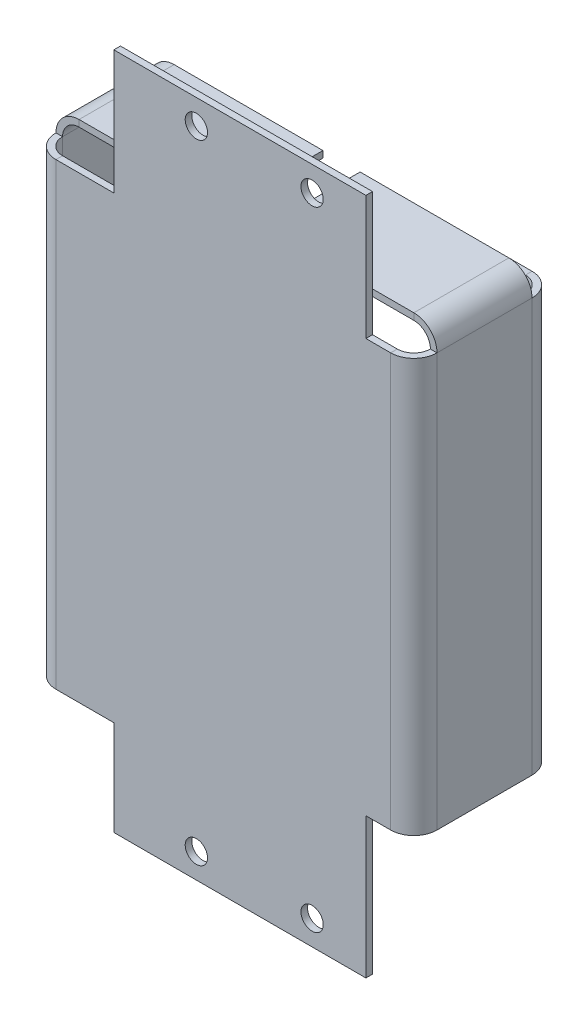
SolidWorks part; units mm, degrees
note: The reader was unsure of these and kept them because the rebuilt part matched: flange length of "Edge-Flange1", "Edge-Flange4", "Edge-Flange5".
ref_plane "Front Plane" through (0, 0, 0) normal (0, 0, 1) x (1, 0, 0)
ref_plane "Top Plane" through (0, 0, 0) normal (0, 1, 0) x (1, 0, 0)
ref_plane "Right Plane" through (0, 0, 0) normal (1, 0, 0) x (0, 0, -1)
sketch "Sketch1" plane through (0, 0, 0) normal (0, 0, 1) x (1, 0, 0)
  line L0 (16.25, 0) -> (16.25, -17)
  line L1 (21.25, 50) -> (16.25, 50)
  line L2 (21.25, 50) -> (21.25, 0)
  line L3 (21.25, 0) -> (16.25, 0)
  line L4 (-23.25, 50) -> (-23.25, -5.5)
  line L5 (16.25, -17) -> (-14.25, -17)
  line L6 (-14.25, -17) -> (-14.25, -5.5)
  line L7 (16.25, 50) -> (16.25, 65)
  line L9 (16.25, 65) -> (-14.25, 65)
  line L10 (-14.25, 65) -> (-14.25, 50)
  line L11 (-14.25, -5.5) -> (-23.25, -5.5)
  line L12 (-14.25, 50) -> (-23.25, 50)
  circle A0 centre (9.7378, -14) radius 1.35
  circle A1 centre (-4.2622, -14) radius 1.35
  circle A2 centre (9.7378, 62) radius 1.35
  circle A3 centre (-4.2622, 62) radius 1.35
  dimension "D6" = 6.5122
  dimension "D7" = 3
  dimension "D8" = 2.7
  dimension "D9" = 3
  dimension "D10" = 14
  dimension "D11" = 76
  dimension "D12" = 14
  dimension "D13" = 3
  dimension "D14" = 3
  dimension "D1" = 50
  dimension "D2" = 9
  dimension "D3" = 82
  dimension "D4" = 17
  dimension "D5" = 30.5
  dimension "D15" = 11.5
  dimension "D16" = 5
sheet metal parameters "Sheet-Metal1" thickness 0.8 parameters "D1"=2
base flange "Base-Flange1" sketch "Sketch1" thickness 0.8 reverse thickness direction yes parameters "D1"=2
edge flange "Edge-Flange1" sketch "Sketch6" flange profiles "Sketch6", "Sketch11" flange angle 90 flange length 13.5 flange position material outside bend radius 2 thickness 0.8 parameters "D6"=10, "D8"=1
sketch "Sketch6" plane through (21.25, 0, 0) normal (-1, 0, 0) x (0, 1, 0)
  line L2 (0, 0) -> (0, 13.5)
  line L3 (0, 13.5) -> (50, 13.5)
  line L4 (50, 13.5) -> (50, 0)
  line L6 (50, 0) -> (0, 0) construction
  line L7 (50, 0) -> (0, 0)
sketch "Sketch11" plane through (-23.25, 0, 0) normal (1, 0, 0) x (0, -1, 0)
  line L0 (5.5, 0) -> (-50, 0) construction
  line L1 (5.5, 0) -> (-50, 0)
  line L2 (5.5, 0) -> (5.5, 13.5)
  line L3 (5.5, 13.5) -> (-50, 13.5)
  line L4 (-50, 13.5) -> (-50, 0)
bend "EdgeBend1" bend radius 2 bend angle 90 parameters "D5"=1
bend "EdgeBend3" bend radius 2 bend angle 90 parameters "D5"=2
edge flange "Edge-Flange4" sketch "Sketch19" flange profiles "Sketch19", "Sketch20" flange angle 90 flange length 20 flange position bend outside bend radius 2 thickness 0.8 parameters "D6"=10, "D8"=1
sketch "Sketch19" plane through (21.25, 50, 0) normal (0, -1, 0) x (0, 0, 1)
  line L2 (-13.5, 0) -> (-13.5, 20)
  line L3 (-13.5, 20) -> (-2, 20)
  line L4 (-2, 20) -> (-2, 0)
  line L6 (-2, 0) -> (-13.5, 0) construction
  line L7 (-2, 0) -> (-13.5, 0)
sketch "Sketch20" plane through (-23.25, 50, 0) normal (0, -1, 0) x (0, 0, -1)
  line L0 (13.5, 0) -> (2, 0) construction
  line L1 (13.5, 0) -> (2, 0)
  line L2 (13.5, 0) -> (13.5, 20)
  line L3 (13.5, 20) -> (2, 20)
  line L4 (2, 20) -> (2, 0)
bend "EdgeBend5" bend radius 2 bend angle 90 parameters "D5"=3
bend "EdgeBend6" bend radius 2 bend angle 90 parameters "D5"=4
edge flange "Edge-Flange5" sketch "Sketch28" flange profiles "Sketch28", "Sketch29" flange angle 90 flange length 10 flange position bend outside bend radius 2 thickness 0.8 parameters "D6"=10, "D8"=1
sketch "Sketch28" plane through (21.25, 0, -13.5) normal (0, 0, 1) x (0, 1, 0)
  line L1 (50, 0) -> (0, 0) construction
  line L2 (0, 0) -> (0, 10)
  line L3 (0, 10) -> (50, 10)
  line L4 (50, 10) -> (50, 0)
  line L5 (50, 0) -> (0, 0)
sketch "Sketch29" plane through (-23.25, 0, -13.5) normal (0, 0, 1) x (0, -1, 0)
  line L0 (5.5, 0) -> (-50, 0) construction
  line L1 (5.5, 0) -> (-50, 0)
  line L2 (5.5, 0) -> (5.5, 10)
  line L3 (5.5, 10) -> (-50, 10)
  line L4 (-50, 10) -> (-50, 0)
bend "EdgeBend7" bend radius 2 bend angle 90 parameters "D5"=5
bend "EdgeBend8" bend radius 2 bend angle 90 parameters "D5"=6
flat pattern "Flat-Pattern1" [suppressed]
sketch "Bend-Lines1" plane through (0, 0, 0.8) normal (0, 0, 1) x (1, 0, 0)
  line L0 (-38.3766, -5.5) -> (-38.3766, 50) construction
  line L1 (36.3766, 50) -> (36.3766, 0) construction
  line L2 (-36.5011, 51.8755) -> (-25.0011, 51.8755) construction
  line L3 (23.0011, 51.8755) -> (34.5011, 51.8755) construction
  line L4 (-23.1255, -5.5) -> (-23.1255, 50) construction
  line L5 (21.1255, 50) -> (21.1255, 0) construction
  line L6 (-38.3766, -5.5) -> (-38.3766, 50) construction
  line L7 (36.3766, 50) -> (36.3766, 0) construction
  line L8 (-36.5011, 51.8755) -> (-25.0011, 51.8755) construction
  line L9 (23.0011, 51.8755) -> (34.5011, 51.8755) construction
  line L10 (-23.1255, -5.5) -> (-23.1255, 50) construction
  line L11 (21.1255, 50) -> (21.1255, 0) construction
sketch3d "Bounding-Box1" [suppressed]
  line L0 (-69.5021, -17, 0) -> (25.0021, -17, 0) construction
  line L1 (-69.5021, 71.7511, 0) -> (25.0021, 71.7511, 0) construction
  line L2 (-69.5021, -17, 0) -> (-69.5021, 71.7511, 0) construction
  line L3 (25.0021, -17, 0) -> (25.0021, 71.7511, 0) construction
bend of the flat pattern "Flatten-<EdgeBend1>1"
bend of the flat pattern "Flatten-<EdgeBend3>1"
bend of the flat pattern "Flatten-<EdgeBend5>1"
bend of the flat pattern "Flatten-<EdgeBend6>1"
bend of the flat pattern "Flatten-<EdgeBend7>1"
bend of the flat pattern "Flatten-<EdgeBend8>1"
fillet "Fillet1" [suppressed] radius 2
fillet "Fillet2" [suppressed] radius 1.88
